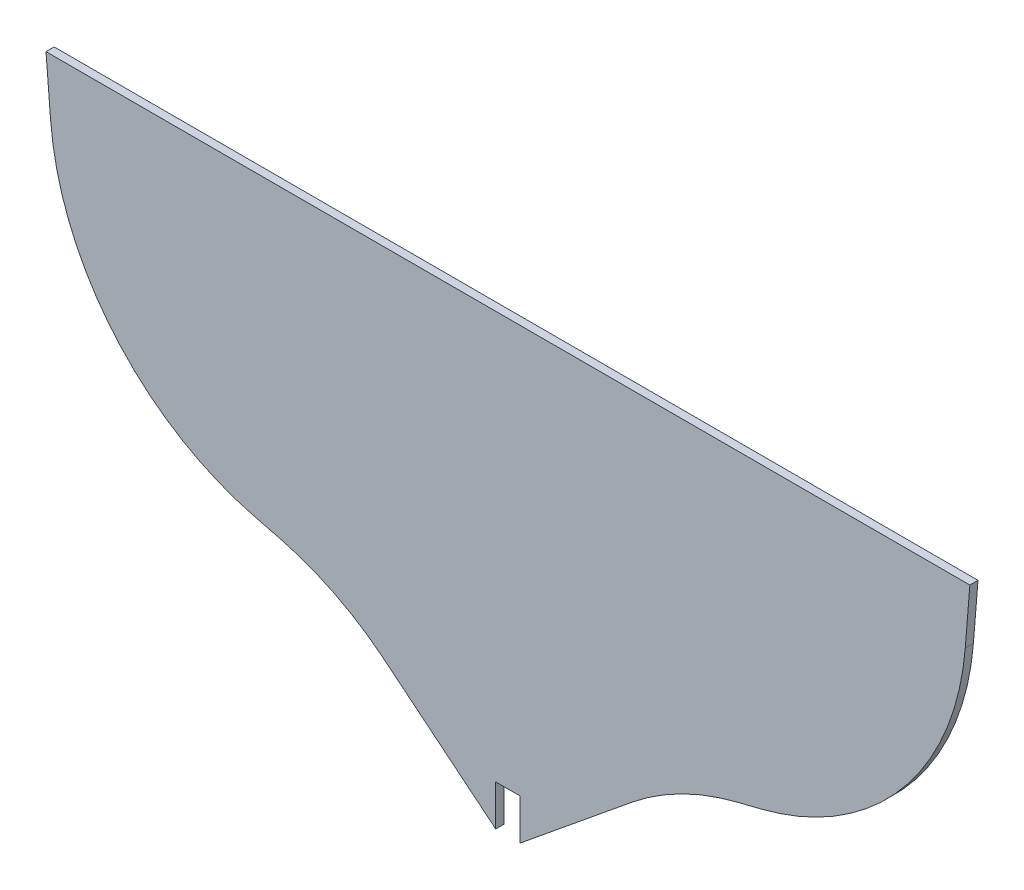
SolidWorks part; units mm, degrees
ref_plane "Plan de face" through (0, 0, 0) normal (0, 0, 1) x (1, 0, 0)
ref_plane "Plan de dessus" through (0, 0, 0) normal (0, 1, 0) x (1, 0, 0)
ref_plane "Plan de droite" through (0, 0, 0) normal (1, 0, 0) x (0, 0, -1)
sketch "Esquisse1" plane through (0, 0, 0) normal (0, 0, 1) x (1, 0, 0)
  line L0 (-133.9234, 132.6316) -> (206.0766, 132.6316)
  line L1 (-133.9234, 132.6316) -> (-126.4395, 40.0765)
  line L3 (31.5766, -32.3684) -> (31.5766, -17.3684)
  line L4 (31.5766, -17.3684) -> (40.5766, -17.3684)
  line L5 (36.0766, 132.6316) -> (36.0766, -17.3684) construction
  line L6 (40.5766, -32.3684) -> (40.5766, -17.3684)
  line L8 (206.0766, 132.6316) -> (198.5926, 40.0765)
  line L9 (31.5766, -32.3684) -> (-26.7334, 15.2474)
  line L10 (-26.7334, 15.2474) -> (-126.4395, 40.0765)
  line L11 (40.5766, -32.3684) -> (98.8866, 15.2474)
  line L12 (98.8866, 15.2474) -> (198.5926, 40.0765)
  dimension "D1" = 170
  dimension "D4" = 9
  dimension "D5" = 15
  dimension "D6" = 150
extrude "Boss.-Extru.1" add sketch "Esquisse1" along normal blind 3
fillet "Congé1" radius 100 4 edges at (198.5926, 40.0765, 1.5) (98.8866, 15.2474, 1.5) (-26.7334, 15.2474, 1.5) (-126.4395, 40.0765, 1.5)
